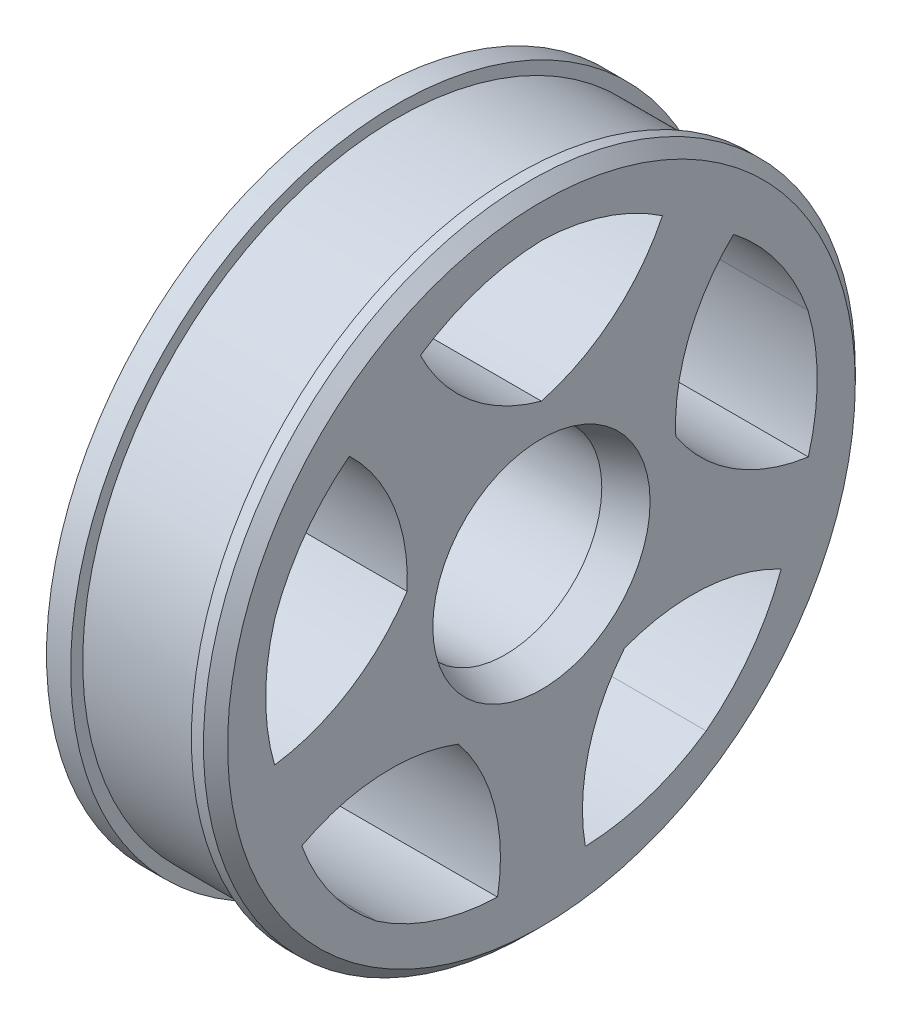
SolidWorks part; units mm, degrees
ref_plane "Front Plane" through (0, 0, 0) normal (0, 0, 1) x (1, 0, 0)
ref_plane "Top Plane" through (0, 0, 0) normal (0, 1, 0) x (1, 0, 0)
ref_plane "Right Plane" through (0, 0, 0) normal (1, 0, 0) x (0, 0, -1)
sketch "Sketch1" plane through (0, 0, 0) normal (1, 0, 0) x (0, 0, -1)
  circle A0 centre (0, 0) radius 13.5
  circle A1 centre (0, 0) radius 4
  dimension "D1" = 27
  dimension "D2" = 8
extrude "Boss-Extrude1" add sketch "Sketch1" along normal mid plane 7
sketch "Sketch2" plane through (0, 0, 0) normal (1, 0, 0) x (0, 0, -1)
  line L0 (0, 0) -> (0, 14.8201) construction
  arc A0 (0, 5.8497) -> (-5.0122, 9.994) centre (2.0377, 13.4173) cw
  arc A1 (-5.0122, 9.994) -> (0, 11.6087) centre (0.2591, 2.218) cw
  arc A2 (5.0122, 9.994) -> (0, 11.6087) centre (-0.2591, 2.218) ccw
  arc A3 (0, 5.8497) -> (5.0122, 9.994) centre (-2.0377, 13.4173) ccw
extrude "Cut-Extrude1" cut sketch "Sketch2" along normal through all both and the other way through all
pattern_circular "CirPattern1" count 5 over 360 about axis through (3.5, 0, 0) along (-1, 0, 0) of "Cut-Extrude1" reverse direction yes
chamfer "Chamfer1" distance 0.5 angle 45 1 edges at (3.5, 0, -13.5)
sketch "Sketch4" plane through (0, 0, 0) normal (1, 0, 0) x (0, 0, -1)
  circle A0 centre (0, 0) radius 13.5
  circle A1 centre (0, 0) radius 13
  circle A2 centre (0, 0) radius 13.5 construction
  dimension "D1" = 0.5
extrude "Cut-Extrude3" cut sketch "Sketch4" against normal mid plane 5
chamfer "Chamfer2" distance 0.5 distance2 1.5 1 edges at (3.5, 0, -4) first distance on face at (3.5, 0, -13)
equation "\"axis_diameter\"=5.66"
equation "\"padding\"=0.5"
